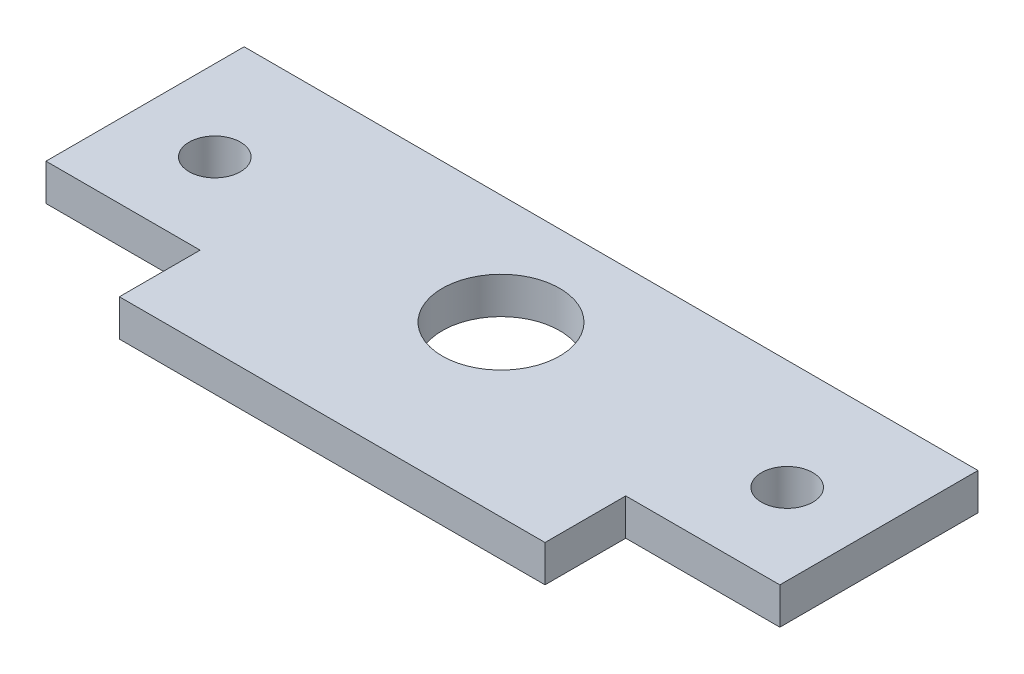
SolidWorks part; units mm, degrees
ref_plane "前视基准面" through (0, 0, 0) normal (0, 0, 1) x (1, 0, 0)
ref_plane "上视基准面" through (0, 0, 0) normal (0, 1, 0) x (1, 0, 0)
ref_plane "右视基准面" through (0, 0, 0) normal (1, 0, 0) x (0, 0, -1)
sketch "草图1" plane through (0, 0, 0) normal (0, 1, 0) x (1, 0, 0)
  line L1 (-50, 15) -> (50, 15)
  line L2 (-50, 15) -> (-50, -23)
  line L3 (-50, -23) -> (50, -23)
  line L4 (50, 15) -> (50, -23)
  line L5 (0, -23) -> (0, 15) construction
  line L6 (-50, 0) -> (50, 0) construction
  circle A0 centre (0, 0) radius 8
  circle A1 centre (39, 0) radius 3.5
  circle A2 centre (-39, 0) radius 3.5
  point P0 (0, 0)
  dimension "D3" = 16
  dimension "D4" = 7
  dimension "D1" = 38
  dimension "D2" = 100
  dimension "D5" = 78
  dimension "D6" = 15
extrude "凸台-拉伸1" add sketch "草图1" along normal blind 5
sketch "草图2" plane through (0, 5, 0) normal (0, 1, 0) x (1, 0, 0)
  line L0 (50, -23) -> (50, 15) construction
  line L1 (29, -23) -> (50, -23)
  line L2 (29, -23) -> (29, -12)
  line L3 (29, -12) -> (50, -12)
  line L4 (50, -23) -> (50, -12)
  line L6 (-50, -23) -> (50, -23) construction
  line L7 (0, 0) -> (0, -23) construction
  line L8 (-50, -23) -> (-50, -12)
  line L9 (-29, -12) -> (-50, -12)
  line L10 (-29, -23) -> (-29, -12)
  line L11 (-29, -23) -> (-50, -23)
  dimension "D1" = 21
  dimension "D2" = 11
extrude "切除-拉伸1" cut sketch "草图2" against normal up to next
